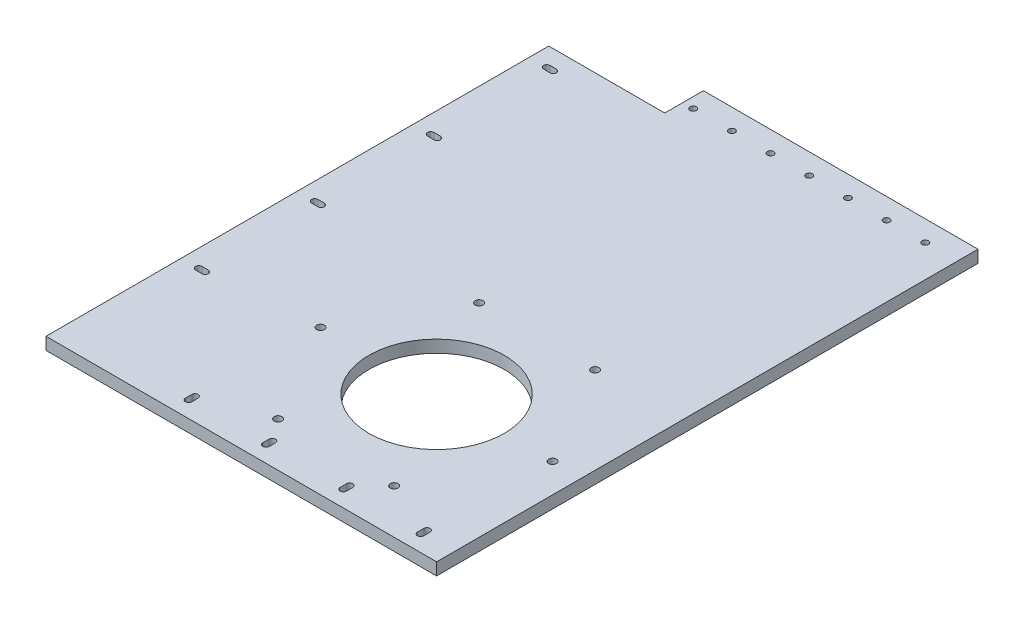
SolidWorks part; units mm, degrees
ref_plane "Front Plane" through (0, 0, 0) normal (0, 0, 1) x (1, 0, 0)
ref_plane "Top Plane" through (0, 0, 0) normal (0, 1, 0) x (1, 0, 0)
ref_plane "Right Plane" through (0, 0, 0) normal (1, 0, 0) x (0, 0, -1)
sketch "Sketch1" plane through (0, 0, 0) normal (0, 1, 0) x (1, 0, 0)
  line L3 (-71, 140) -> (71, 140)
  line L4 (71, -140) -> (71, 140)
  line L5 (0, 140) -> (0, -135) construction
  line L6 (0, 0) -> (71, 0) construction
  line L10 (-71, 140) -> (-71, 120)
  line L11 (-71, 120) -> (-131, 120)
  line L12 (-131, 120) -> (-131, -140)
  line L13 (-131, -140) -> (71, -140)
  point P0 (0, 0)
  dimension "D1" = 280
  dimension "D2" = 20
  dimension "D3" = 202
  dimension "D4" = 60
extrude "Boss-Extrude1" add sketch "Sketch1" along normal blind 6.35
sketch "Sketch2" plane through (0, 6.35, 0) normal (0, 1, 0) x (1, 0, 0)
  line L1 (0, 140) -> (0, -140) construction
  line L2 (71, 140) -> (-71, 140) construction
  line L3 (-131, -140) -> (71, -140) construction
  circle A0 centre (0, -65) radius 41.5 construction
  circle A1 centre (0, -23.5) radius 2.25
  circle A2 centre (29.3449, -35.6551) radius 2.25
  circle A3 centre (41.5, -65) radius 2.25
  circle A4 centre (29.3449, -94.3449) radius 2.25
  circle A5 centre (0, -106.5) radius 2.25
  circle A6 centre (-29.3449, -94.3449) radius 2.25
  circle A7 centre (-41.5, -65) radius 2.25
  circle A8 centre (-29.3449, -35.6551) radius 2.25
  circle A9 centre (0, -65) radius 80 construction
  circle A10 centre (0, -65) radius 30
  point P22 (0, -65)
  dimension "D1" = 83
  dimension "D2" = 4.5
  dimension "D4" = 160
  dimension "D6" = 60
  dimension "D5" = 75
  dimension "D3" = 8
extrude "Cut-Extrude1" [suppressed] cut sketch "Sketch2" against normal through all
sketch "Sketch6" [suppressed] plane through (0, 6.35, 0) normal (0, 1, 0) x (1, 0, 0)
  line L0 (0, -65) -> (-38.9712, -46.8274) construction
  line L1 (0, -65) -> (0, -23.5) construction
  line L2 (-40.9787, -51.1324) -> (-36.9638, -42.5225) construction
  line L3 (-36.9638, -42.5225) -> (-27.9007, -46.7486) construction
  circle A0 centre (0, -65) radius 30 construction
  circle A1 centre (-36.9638, -42.5225) radius 0.85
  circle A2 centre (-40.9787, -51.1324) radius 0.85
  circle A5 centre (-29.9082, -51.0536) radius 0.85
  point P7 (-38.9712, -46.8274)
  dimension "D4" = 1.7
  dimension "D5" = 10
  dimension "D7" = 10
  dimension "D6" = 1.7
  dimension "D1" = 43
  dimension "D2" = 9.5
  dimension "D3" = 65
extrude "Cut-Extrude5" [suppressed] cut sketch "Sketch6" against normal through all
sketch "Sketch8" [suppressed] plane through (0, 6.35, 0) normal (0, 1, 0) x (1, 0, 0)
  line L1 (71, 140) -> (-71, 140) construction
  line L2 (65, -20.6305) -> (65, 140) construction
  line L3 (71, -140) -> (71, 140) construction
  line L5 (45, 41.8036) -> (45, 140) construction
  circle A0 centre (0, 65) radius 25
  circle A1 centre (0, -65) radius 30 construction
  dimension "D1" = 130
  dimension "D2" = 50
  dimension "D3" = 6
  dimension "D4" = 20
extrude "Cut-Extrude9" [suppressed] cut sketch "Sketch8" against normal through all
sketch "Sketch9" plane through (0, 0, 0) normal (0, -1, 0) x (-1, 0, 0)
  circle A1 centre (45.6, 129.325) radius 1.65
  circle A2 centre (5.6, 129.325) radius 1.65
  circle A3 centre (-34.4, 129.325) radius 1.65
  circle A4 centre (65.6, 129.325) radius 1.65
  circle A5 centre (25.6, 129.325) radius 1.65
  circle A6 centre (-14.4, 129.325) radius 1.65
  circle A7 centre (-54.4, 129.325) radius 1.65
extrude "Cut-Extrude10" cut sketch "Sketch9" against normal blind 30
sketch "Sketch10" plane through (0, 0, 0) normal (0, -1, 0) x (1, 0, 0)
  line L0 (-121.975, 10) -> (-118.675, 10) construction
  line L3 (-121.975, 11.65) -> (-118.675, 11.65)
  line L4 (-121.975, 8.35) -> (-118.675, 8.35)
  line L5 (-121.975, 70) -> (-118.675, 70) construction
  line L6 (-121.975, 71.65) -> (-118.675, 71.65)
  line L7 (-121.975, 68.35) -> (-118.675, 68.35)
  line L8 (-121.975, -50) -> (-118.675, -50) construction
  line L9 (-121.975, -48.35) -> (-118.675, -48.35)
  line L10 (-121.975, -51.65) -> (-118.675, -51.65)
  line L11 (-121.975, -110) -> (-118.675, -110) construction
  line L12 (-121.975, -108.35) -> (-118.675, -108.35)
  line L13 (-121.975, -111.65) -> (-118.675, -111.65)
  circle A0 centre (-120.325, -110) radius 1.65
  circle A1 centre (-120.325, -50) radius 1.65
  circle A2 centre (-120.325, 10) radius 1.65
  circle A3 centre (-120.325, 70) radius 1.65
  arc A6 (-121.975, 11.65) -> (-121.975, 8.35) centre (-121.975, 10) ccw
  arc A7 (-118.675, 8.35) -> (-118.675, 11.65) centre (-118.675, 10) ccw
  arc A8 (-121.975, 71.65) -> (-121.975, 68.35) centre (-121.975, 70) ccw
  arc A9 (-118.675, 68.35) -> (-118.675, 71.65) centre (-118.675, 70) ccw
  arc A10 (-121.975, -48.35) -> (-121.975, -51.65) centre (-121.975, -50) ccw
  arc A11 (-118.675, -51.65) -> (-118.675, -48.35) centre (-118.675, -50) ccw
  arc A12 (-121.975, -108.35) -> (-121.975, -111.65) centre (-121.975, -110) ccw
  arc A13 (-118.675, -111.65) -> (-118.675, -108.35) centre (-118.675, -110) ccw
  point P14 (-120.325, 10)
  point P21 (-120.325, 70)
  point P28 (-120.325, -50)
  point P35 (-120.325, -110)
  dimension "D1" = 3.3
  dimension "D2" = 3.3
  dimension "D3" = 3.3
  dimension "D4" = 3.3
  dimension "D5" = 1.65
  dimension "D6" = 1.65
  dimension "D7" = 1.65
  dimension "D8" = 1.65
sketch "Sketch11" plane through (0, 6.35, 0) normal (0, 1, 0) x (1, 0, 0)
  line L0 (71, -127.15) -> (-131, -127.15) construction
  line L1 (71, -140) -> (71, 140) construction
  line L2 (456.625, -127.15) -> (-127.825, -127.15) construction
  line L3 (-131, 120) -> (-131, -140) construction
  line L4 (71, -132.85) -> (-131, -132.85) construction
  line L5 (456.625, -132.85) -> (-127.825, -132.85) construction
  line L6 (-65.6, 129.325) -> (-65.6, -130.005) construction
  line L7 (-65.6, -130.005) -> (71, -130) construction
  line L8 (456.625, -130) -> (-127.825, -130) construction
  line L9 (-25.6, 129.325) -> (-25.6, -130.0035) construction
  line L10 (14.4, 129.325) -> (14.4, -130.0021) construction
  line L11 (54.4, 129.325) -> (54.4, -130.0006) construction
  line L12 (-65.6, -128.355) -> (-65.6, -131.655) construction
  line L13 (-63.95, -128.355) -> (-63.95, -131.655)
  line L14 (-67.25, -128.355) -> (-67.25, -131.655)
  line L15 (-25.6, -128.3535) -> (-25.6, -131.6535) construction
  line L16 (-23.95, -128.3535) -> (-23.95, -131.6535)
  line L17 (-27.25, -128.3535) -> (-27.25, -131.6535)
  line L18 (14.4, -128.3521) -> (14.4, -131.6521) construction
  line L19 (16.05, -128.3521) -> (16.05, -131.6521)
  line L20 (12.75, -128.3521) -> (12.75, -131.6521)
  line L21 (54.4, -128.3506) -> (54.4, -131.6506) construction
  line L22 (56.05, -128.3506) -> (56.05, -131.6506)
  line L23 (52.75, -128.3506) -> (52.75, -131.6506)
  circle A0 centre (-65.6, -130.005) radius 1.65 construction
  circle A1 centre (-25.6, -130.0035) radius 1.65 construction
  circle A2 centre (14.4, -130.0021) radius 1.65 construction
  circle A3 centre (54.4, -130.0006) radius 1.65 construction
  arc A4 (-63.95, -128.355) -> (-67.25, -128.355) centre (-65.6, -128.355) ccw
  arc A5 (-67.25, -131.655) -> (-63.95, -131.655) centre (-65.6, -131.655) ccw
  arc A6 (-23.95, -128.3535) -> (-27.25, -128.3535) centre (-25.6, -128.3535) ccw
  arc A7 (-27.25, -131.6535) -> (-23.95, -131.6535) centre (-25.6, -131.6535) ccw
  arc A8 (16.05, -128.3521) -> (12.75, -128.3521) centre (14.4, -128.3521) ccw
  arc A9 (12.75, -131.6521) -> (16.05, -131.6521) centre (14.4, -131.6521) ccw
  arc A10 (56.05, -128.3506) -> (52.75, -128.3506) centre (54.4, -128.3506) ccw
  arc A11 (52.75, -131.6506) -> (56.05, -131.6506) centre (54.4, -131.6506) ccw
  point P33 (-65.6, -130.005)
  point P39 (-25.6, -130.0035)
  point P46 (14.4, -130.0021)
  point P53 (54.4, -130.0006)
  dimension "D2" = 3.3
  dimension "D1" = 259.33
extrude "Cut-Extrude12" cut sketch "Sketch11" against normal blind 30
extrude "Cut-Extrude13" cut sketch "Sketch10" against normal blind 10 contours A0 | L13 A13 L12 A0 | L12 A12 L13 A0 | L9 A10 L10 A1 | A1 | L10 A11 L9 A1 | L3 A6 L4 A2 | A2 | L4 A7 L3 A2 | L6 A8 L7 A3 | A3 | L7 A9 L6 A3 region at (-122.4459, 0, 10) region at (-118.2041, 0, 10) region at (-120.325, 0, 10) region at (-122.4459, 0, 70) region at (-118.2041, 0, 70) region at (-120.325, 0, 70) region at (-122.4459, 0, -50) region at (-118.2041, 0, -50) region at (-120.325, 0, -50) region at (-122.4459, 0, -110) region at (-118.2041, 0, -110) region at (-120.325, 0, -110)
sketch "Sketch12" plane through (0, 6.35, 0) normal (0, 1, 0) x (1, 0, 0)
  line L0 (-131, -140) -> (71, -140) construction
  line L1 (71, -140) -> (71, 140) construction
  circle A0 centre (-4, -65) radius 35
  dimension "D1" = 70
  dimension "D2" = 75
  dimension "D3" = 75
extrude "Cut-Extrude14" cut sketch "Sketch12" against normal through all
sketch "Sketch13" plane through (0, 6.35, 0) normal (0, 1, 0) x (1, 0, 0)
  line L0 (-69, -65) -> (-59, -65) construction
  circle A2 centre (-4, -65) radius 65 construction
  circle A3 centre (-64, -65) radius 2
  circle A4 centre (-34, -13.0385) radius 2
  circle A5 centre (-4, -65) radius 65 construction
  circle A6 centre (26, -13.0385) radius 2
  circle A7 centre (-4, -65) radius 65 construction
  circle A8 centre (56, -65) radius 2
  circle A9 centre (-4, -65) radius 65 construction
  circle A10 centre (26, -116.9615) radius 2
  circle A11 centre (-4, -65) radius 65 construction
  circle A12 centre (-34, -116.9615) radius 2
  circle A13 centre (-4, -65) radius 65 construction
  circle A14 centre (-4, -65) radius 55 construction
  circle A15 centre (-4, -65) radius 35 construction
  point P25 (-4, -65)
  dimension "D1" = 130
  dimension "D2" = 4
  dimension "D3" = 6
  dimension "D4" = 110
extrude "Cut-Extrude15" cut sketch "Sketch13" against normal through all
